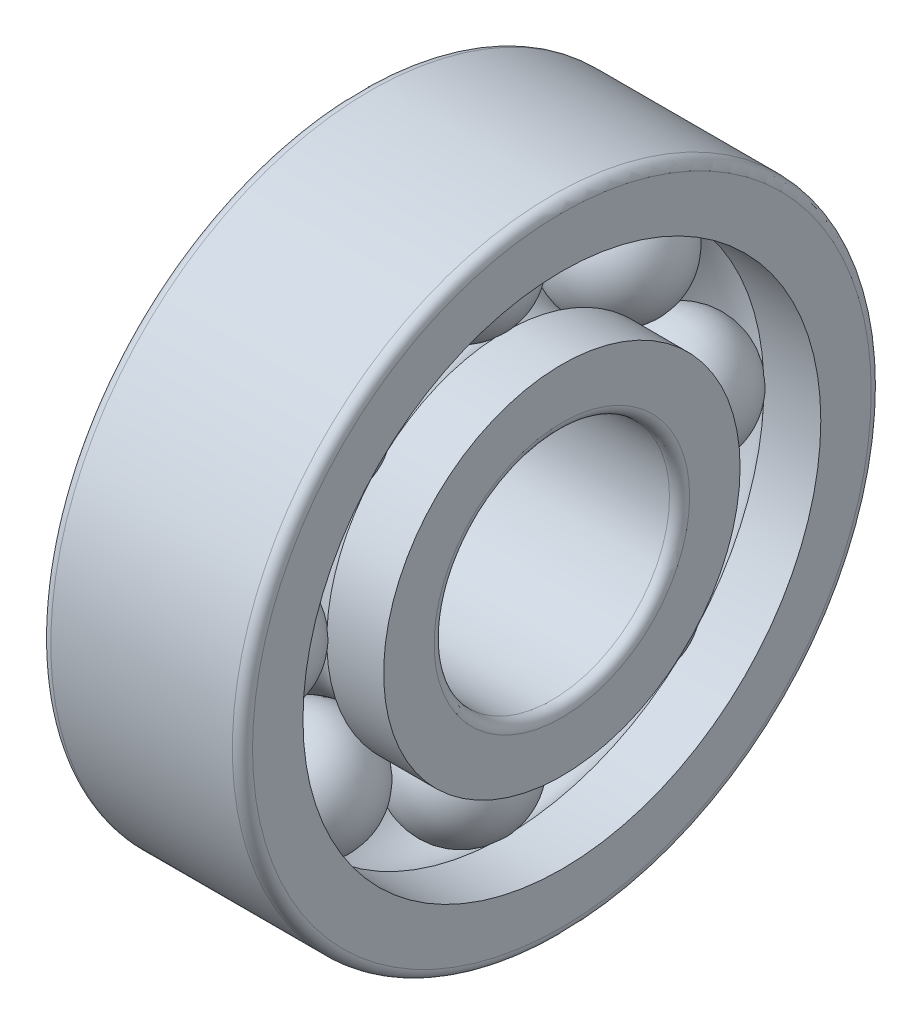
SolidWorks part; units mm, degrees
material "Alliage de zinc AC41A, brut"
ref_plane "Plane1" through (0, 0, 0) normal (0, 0, 1) x (1, 0, 0)
ref_plane "Plane2" through (0, 0, 0) normal (0, 1, 0) x (1, 0, 0)
ref_plane "Plane3" through (0, 0, 0) normal (1, 0, 0) x (0, 0, -1)
other "Configuration Table"
sketch "Clipboard" plane through (0, 0, 0) normal (0, 0, 1) x (1, 0, 0)
  line L0 (-10, 0) -> (10, 0) construction
  line L1 (0, 0) -> (22.1431, -3.112)
  line L2 (0, 0) -> (6.4367, 0.9046)
  line L3 (0, 0) -> (22.1431, -3.112)
  line L4 (0, 0) -> (-22.3573, -0.3902)
  dimension "BallCLRad" = 6.5
sketch "CagSpiSke" plane through (0, 0, 0) normal (0, 0, 1) x (1, 0, 0)
  line L0 (0.18, 6.2) -> (0.18, 6.8)
  line L1 (0.18, 6.8) -> (-0.18, 6.8)
  line L2 (-0.18, 6.8) -> (-0.18, 6.2)
  line L3 (-0.18, 6.2) -> (0.18, 6.2)
  line L4 (-20.6375, 0) -> (20.6375, 0) construction
  line L5 (0, 0) -> (0, 23.7692) construction
  dimension "OD" = 13.6
  dimension "ID" = 12.4
revolve "CageSpine" add sketch "CagSpiSke" angle 0.001 about L4 reverse direction yes
ref_axis "Axis1" through (-50, 0, 0) along (1, 0, 0)
sketch "CagBalSke" plane through (0, 0, 0) normal (0, 0, 1) x (1, 0, 0)
  line L0 (-1.98, 6.5) -> (1.98, 6.5)
  line L1 (-1.905, 6.5) -> (1.905, 6.5) construction
  line L2 (-10, 0) -> (10, 0) construction
  line L3 (0, 0) -> (0, 24) construction
  arc A0 (1.98, 6.5) -> (-1.98, 6.5) centre (0, 6.5) cw
  dimension "BallCLRad" = 6.5
revolve "CageBall" [suppressed] add sketch "CagBalSke" angle 360 about L1 reverse direction yes
pattern_circular "CageBalls" [suppressed] count 8 every 45 about axis through (-50, 0, 0) along (1, 0, 0)
sketch "CagTrmODSke" plane through (0, 0, 0) normal (0, 0, 1) x (1, 0, 0)
  line L0 (1.981, 6.8) -> (1.981, 8.481)
  line L1 (1.981, 8.481) -> (-1.981, 8.481)
  line L2 (-1.981, 8.481) -> (-1.981, 6.8)
  line L3 (-1.981, 6.8) -> (1.981, 6.8)
  line L4 (-20.6375, 0) -> (20.6375, 0) construction
  line L5 (0, 0) -> (0, 25) construction
  dimension "Width" = 3.962
  dimension "ID" = 13.6
  dimension "OD" = 16.962
revolve "CageTrimOD" [suppressed] cut sketch "CagTrmODSke" angle 360 about L4 reverse direction yes
sketch "CagTrmIDSke" plane through (0, 0, 0) normal (0, 0, 1) x (1, 0, 0)
  line L0 (1.981, 4.521) -> (1.981, 6.2)
  line L1 (1.981, 6.2) -> (-1.981, 6.2)
  line L2 (-1.981, 6.2) -> (-1.981, 4.521)
  line L3 (-1.981, 4.521) -> (1.981, 4.521)
  line L4 (-20.6375, 0) -> (20.6375, 0) construction
  line L5 (0, 0) -> (0, 25) construction
  dimension "Width" = 3.962
  dimension "ID" = 9.042
  dimension "OD" = 12.4
revolve "CageTrimID" [suppressed] cut sketch "CagTrmIDSke" angle 360 about L4 reverse direction yes
sketch "BalSimSke" plane through (0, 0, 0) normal (0, 0, 1) x (1, 0, 0)
  line L0 (-10, 0) -> (10, 0) construction
  line L1 (-10, 6.5) -> (10, 6.5) construction
  line L2 (0, 0) -> (0, 23) construction
  circle A0 centre (0, 6.5) radius 1.8
  dimension "BallCLRad" = 6.5
  dimension "Ball_diameter" = 3.6
revolve "BallsSimplified" [suppressed] add sketch "BalSimSke" angle 360 about L0
sketch "BalDetSke" plane through (0, 0, 0) normal (0, 0, 1) x (1, 0, 0)
  line L0 (-1.8, 6.5) -> (1.8, 6.5)
  line L1 (-1.905, 6.5) -> (1.905, 6.5) construction
  line L2 (0, 0) -> (0, 25) construction
  arc A0 (1.8, 6.5) -> (-1.8, 6.5) centre (0, 6.5) cw
  dimension "BallCLRad" = 6.5
  dimension "Ball_diameter" = 3.6
revolve "BallDetailed" add sketch "BalDetSke" angle 360 about L1 reverse direction yes
sketch "InnRacSke" plane through (0, 0, 0) normal (0, 0, 1) x (1, 0, 0)
  line L0 (-1.3079, 5.3) -> (-3, 5.3)
  line L1 (-3, 5.3) -> (-3, 3.8)
  line L2 (-2.7, 3.5) -> (2.7, 3.5)
  line L3 (3, 3.8) -> (3, 5.3)
  line L4 (3, 5.3) -> (1.3079, 5.3)
  line L5 (-20.6375, 0) -> (20.6375, 0) construction
  line L6 (0, 0) -> (0, 30) construction
  arc A0 (-3, 3.8) -> (-2.7, 3.5) centre (-2.7, 3.8) ccw
  arc A1 (2.7, 3.5) -> (3, 3.8) centre (2.7, 3.8) ccw
  arc A2 (1.3079, 5.3) -> (-1.3079, 5.3) centre (0, 6.5) cw
  dimension "BallCLRad" = 6.5
  dimension "Fillet_radius" = 0.3
  dimension "Ball_diameter" = 3.55
  dimension "ID" = 7
  dimension "OD" = 10.6
  dimension "Width" = 6
revolve "InnerRace" add sketch "InnRacSke" angle 360 about L5 reverse direction yes
sketch "OutRacSke" plane through (0, 0, 0) normal (0, 0, 1) x (1, 0, 0)
  line L0 (-1.3079, 7.7) -> (-3, 7.7)
  line L1 (-3, 7.7) -> (-3, 9.2)
  line L2 (-2.7, 9.5) -> (2.7, 9.5)
  line L3 (3, 9.2) -> (3, 7.7)
  line L4 (3, 7.7) -> (1.3079, 7.7)
  line L5 (-20.6375, 0) -> (20.6375, 0) construction
  line L6 (0, 0) -> (0, 30) construction
  arc A0 (-3, 9.2) -> (-2.7, 9.5) centre (-2.7, 9.2) cw
  arc A1 (2.7, 9.5) -> (3, 9.2) centre (2.7, 9.2) cw
  arc A2 (1.3079, 7.7) -> (-1.3079, 7.7) centre (0, 6.5) ccw
  dimension "BallCLRad" = 6.5
  dimension "Fillet_radius" = 0.3
  dimension "Ball_diameter" = 3.55
  dimension "Width" = 6
revolve "OuterRace" add sketch "OutRacSke" angle 360 about L5 reverse direction yes
pattern_circular "BallsDetailed" count 8 every 45 about axis through (-50, 0, 0) along (1, 0, 0) of "BallDetailed"
equation "\"BallCLRad@Clipboard\" = ( \"OD@OutRacSke\" + \"ID@InnRacSke\" ) / 4"
equation "\"BallCLRad@BalSimSke\" = \"BallCLRad@Clipboard\""
equation "\"BallCLRad@BalDetSke\" = \"BallCLRad@Clipboard\""
equation "\"BallCLRad@InnRacSke\" = \"BallCLRad@Clipboard\""
equation "\"BallCLRad@OutRacSke\" = \"BallCLRad@Clipboard\""
equation "\"Ball_diameter@InnRacSke\" = \"Ball_diameter@BalDetSke\" - 0.05"
equation "\"Ball_diameter@OutRacSke\" = \"Ball_diameter@BalDetSke\" - 0.05"
equation "\"Ball_diameter@BalSimSke\" = \"Ball_diameter@BalDetSke\""
equation "\"Width@OutRacSke\" = \"Width@InnRacSke\""
equation "\"Fillet_radius@OutRacSke\" = \"Fillet_radius@InnRacSke\""
equation "\"Max_count@Clipboard\" = int( 3.14159265 / atn(( \"Ball_diameter@BalDetSke\" / 2) / sqr( \"BallCLRad@Clipboard\"  *  \"BallCLRad@Clipboard\" - ( \"Ball_diameter@BalDetSke\" / 2) *  ( \"Ball_diameter@BalDetSke\" / 2))))"
equation "\"Max_count@Clipboard\" = ((sgn( \"Max_count@Clipboard\" - \"Count@Clipboard\" )-1)*( \"Max_count@Clipboard\" - \"Count@Clipboard\" ))/-2+ \"Count@Clipboard\""
equation "\"Count@BallsDetailed\" = int( \"Show_count@Clipboard\" ) "
equation "\"Count@BallsDetailed\" = ((sgn( \"Count@BallsDetailed\" - \"Max_count@Clipboard\" )-1)*( \"Count@BallsDetailed\" - \"Max_count@Clipboard\" ))/-2+ \"Max_count@Clipboard\""
equation "\"Count@BallsDetailed\" = ((sgn( \"Count@BallsDetailed\" - \"Min_count@Clipboard\" )+1)*( \"Count@BallsDetailed\" - \"Min_count@Clipboard\"))/2 +\"Min_count@Clipboard\""
equation "\"Angle@BallsDetailed\" = 360.0 / \"Max_count@Clipboard\""
equation "\"BallCLRad@CagBalSke\" = \"BallCLRad@Clipboard\""
equation "\"Count@CageBalls\" = \"Count@BallsDetailed\""
equation "\"Angle@CageBalls\" = \"Angle@BallsDetailed\""
equation "\"Angle@CageSpine\" =  \"Angle@CageBalls\" * ( \"Count@CageBalls\" -1 + int( \"Count@CageBalls\" / \"Max_count@Clipboard\" ) )  + 0.001 -  int( \"Count@CageBalls\" / \"Max_count@Clipboard\" ) * 0.001"
equation "\"Angle@CageSpine\" =  \"Angle@CageSpine\" * int( \"Min_count@Clipboard\" / 2) + int(1 / \"Min_count@Clipboard\")  * 0.001"
equation "\"CageWallOD@CagBalSke\" =  \"Ball_diameter@BalDetSke\" * 1.1"
equation "\"Thickness@CagSpiSke\" =  \"Ball_diameter@BalDetSke\" * 0.1"
equation "\"OD@CagTrmODSke\" = \"BallCLRad@Clipboard\" * 2 + \"CageWallOD@CagBalSke\" + 0.002"
equation "\"ID@CagTrmODSke\" = \"BallCLRad@Clipboard\" * 2 + \"Ball_diameter@BalDetSke\" / 6"
equation "\"OD@CagTrmIDSke\" = \"BallCLRad@Clipboard\" * 2 - \"Ball_diameter@BalDetSke\" / 6"
equation "\"ID@CagTrmIDSke\" = \"BallCLRad@Clipboard\" * 2 - \"CageWallOD@CagBalSke\" + 0.002"
equation "\"OD@CagSpiSke\" = \"ID@CagTrmODSke\""
equation "\"ID@CagSpiSke\" = \"OD@CagTrmIDSke\""
equation "\"Width@CagTrmODSke\" = \"CageWallOD@CagBalSke\" + 0.002"
equation "\"Width@CagTrmIDSke\" = \"CageWallOD@CagBalSke\" + 0.002"
